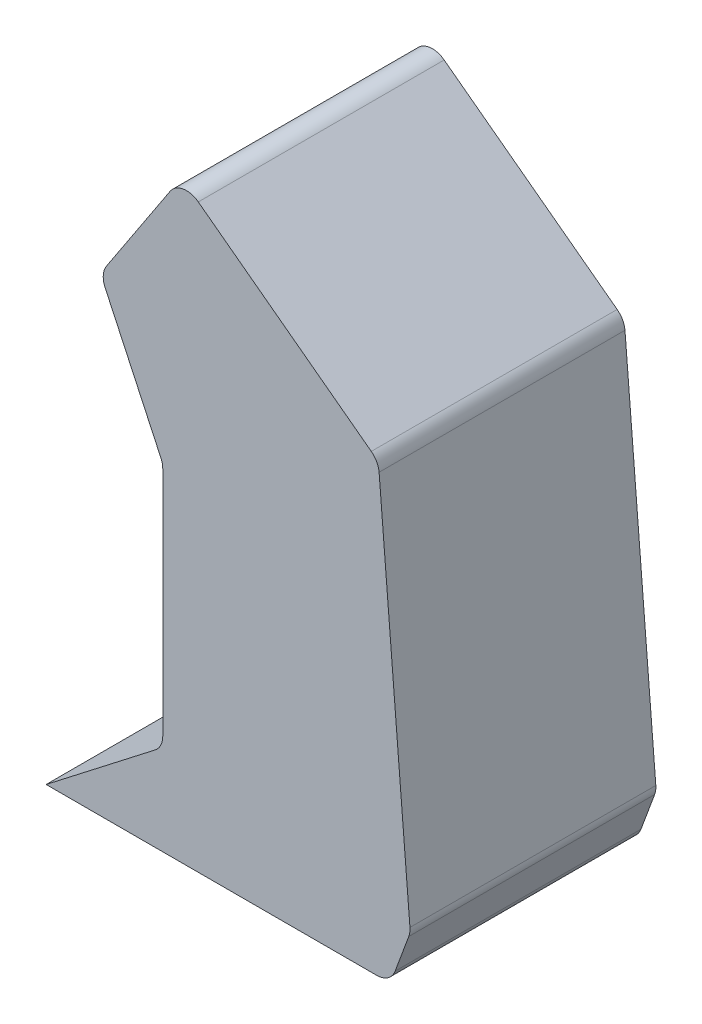
SolidWorks part; units mm, degrees
ref_plane "Alzado" through (0, 0, 0) normal (0, 0, 1) x (1, 0, 0)
ref_plane "Planta" through (0, 0, 0) normal (0, 1, 0) x (1, 0, 0)
ref_plane "Vista lateral" through (0, 0, 0) normal (1, 0, 0) x (0, 0, -1)
sketch "Sketch5" plane through (0, 0, 0) normal (0, 0, 1) x (1, 0, 0)
  line L0 (0, 0) -> (672.1713, 0)
  line L3 (661.2211, 917.2038) -> (309.4273, 1180.6252)
  line L5 (119.8339, 935.3098) -> (233.4472, 691.7171)
  line L6 (237.1963, 674.8094) -> (237.1963, 203.2949)
  line L7 (221.6868, 171.6687) -> (0, 0)
  line L8 (252.0481, 1170.6107) -> (122.681, 974.2215)
  line L9 (677.1139, 888.4318) -> (739.8353, 118.2036)
  line L10 (737.4717, 101.0495) -> (709.6757, 26.0924)
  arc A0 (677.1139, 888.4318) -> (661.2211, 917.2038) centre (637.2459, 885.1853) ccw
  arc A1 (739.8353, 118.2036) -> (737.4717, 101.0495) centre (699.9673, 114.957) cw
  arc A2 (672.1713, 0) -> (709.6757, 26.0924) centre (672.1713, 40) ccw
  arc A3 (237.1963, 203.2949) -> (221.6868, 171.6687) centre (197.1963, 203.2949) cw
  arc A4 (233.4472, 691.7171) -> (237.1963, 674.8094) centre (197.1963, 674.8094) cw
  arc A5 (122.681, 974.2215) -> (119.8339, 935.3098) centre (156.0849, 952.2175) ccw
  arc A6 (309.4273, 1180.6252) -> (252.0481, 1170.6107) centre (285.452, 1148.6066) ccw
  point P2 (820.8028, 101.0634)
  point P10 (0, 0)
  point P11 (977.9432, 1028.76)
  point P12 (955.2241, 663.0907)
  point P13 (251.2402, 663.0907)
  point P14 (211.1736, 992.7881)
  point P15 (0, 0)
  point P16 (932.505, 714.4791)
  point P19 (675.6508, 906.3989)
  point P24 (700, 0)
  point P27 (237.1963, 183.6789)
  point P30 (237.1963, 683.6789)
  point P33 (110.3887, 955.5609)
  point P36 (275.4193, 1206.0901)
  point P37 (0, 0)
  point P38 (289.5072, 578.6485)
  point P39 (342.5448, 969.6599)
  point P40 (273.873, 109.9956)
  point P41 (700, 733.3963)
  point P42 (450.6742, 40)
  point P43 (708.8274, 162.7133)
  point P44 (708.8274, 0)
  point P45 (477.7066, 40)
  point P46 (700, 115.6629)
  point P47 (93.4244, 1046.6953)
  point P48 (116.5125, 955.0353)
  point P49 (672.2594, 904.5257)
  dimension "D5" = 40
  dimension "D1" = 300
  dimension "D2" = 500
  dimension "D3" = 300
  dimension "D4" = 500
  dimension "D7" = 700
  dimension "D8" = 300
extrude "Boss-Extrude4" add sketch "Sketch5" along normal blind 250 and the other way blind 250
